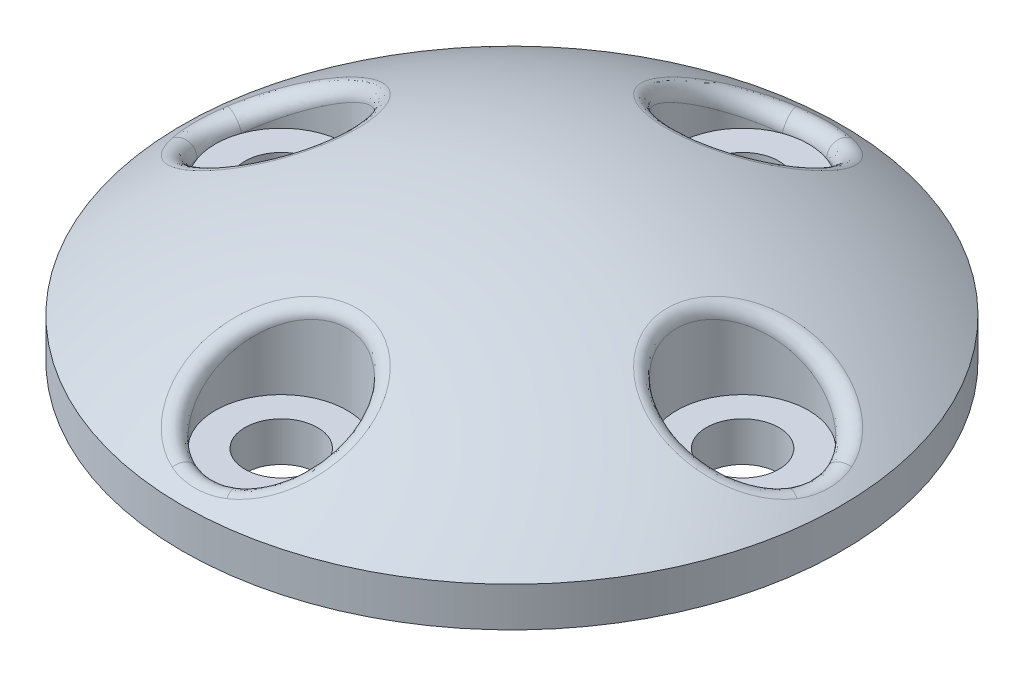
SolidWorks part; units mm, degrees
ref_plane "Front" through (0, 0, 0) normal (0, 0, 1) x (1, 0, 0)
ref_plane "Top" through (0, 0, 0) normal (0, 1, 0) x (1, 0, 0)
ref_plane "Right" through (0, 0, 0) normal (1, 0, 0) x (0, 0, -1)
sketch "Sketch2" plane through (0, 0, 0) normal (0, 1, 0) x (1, 0, 0)
  circle A0 centre (0, 0) radius 25
  dimension "D1" = 50
extrude "Boss-Extrude1" add sketch "Sketch2" along normal blind 3
dome "Dome1" faces to dome 1 distance 8 reverse direction no elliptical dome no face at (0, 3, 25) parameters "D1"=8
hole_wizard "M5 Clearance Hole1" positions "Sketch5" profile "Sketch6" hole size "M5" standard "ANSI Metric" end condition up to next
sketch "Sketch5" plane through (0, 0, 0) normal (0, -1, 0) x (-1, 0, 0)
  line L0 (0, 0) -> (0, -17.5) construction
  circle A0 centre (0, 0) radius 17.5
  point P0 (0, -17.5)
  point P12 (0, -17.5)
  dimension "D1" = 35
sketch "Sketch6" plane through (0, 0, 17.5) normal (1, 0, 0) x (0, 0, -1)
  line L0 (0, 0) -> (0, 11.001)
  line L1 (0, 11.001) -> (2.75, 11.001)
  line L2 (2.75, 11.001) -> (2.75, 0)
  line L5 (2.75, 0) -> (0, 0)
  line L11 (0, -6.35) -> (0, 107.95) construction
  dimension "Thru Hole Dia." = 5.5
  dimension "Thru Hole Depth" = 11.001
pattern_circular "CirPattern1" count 4 over 360 about axis through (0, 0, 0) along (0, 1, 0) of "M5 Clearance Hole1"
sketch "Sketch7" plane through (0, 0, 0) normal (0, -1, 0) x (1, 0, 0)
  circle A0 centre (-17.5, 0) radius 5
  circle A1 centre (0, 17.5) radius 5
  circle A2 centre (17.5, 0) radius 5
  circle A3 centre (0, -17.5) radius 5
  dimension "D1" = 10
extrude "Cut-Extrude2" cut sketch "Sketch7" against normal through all from offset 3 offset against normal yes
fillet "Fillet1" radius 1 4 edges at (4.3024, 8.0908, -14.9525) (19.247, 6.1734, 4.6849) (4.9475, 7.2876, 16.777) (-13.2742, 8.8158, 2.6725)
